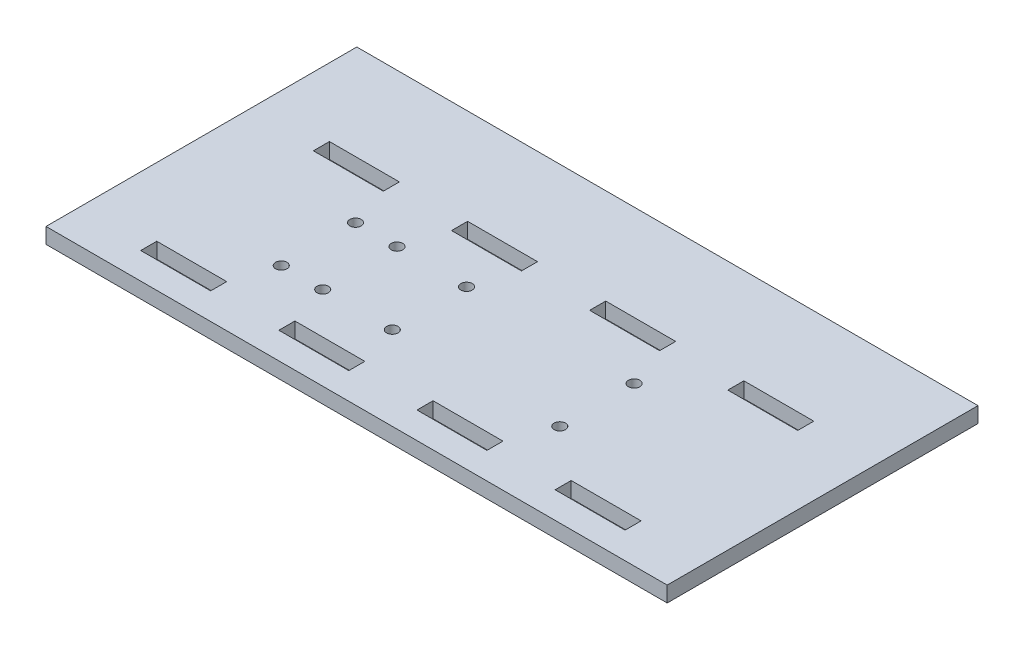
SolidWorks part; units mm, degrees
ref_plane "Front Plane" through (0, 0, 0) normal (0, 0, 1) x (1, 0, 0)
ref_plane "Top Plane" through (0, 0, 0) normal (0, 1, 0) x (1, 0, 0)
ref_plane "Right Plane" through (0, 0, 0) normal (1, 0, 0) x (0, 0, -1)
sketch "Sketch2" plane through (0, 0, 0) normal (0, 1, 0) x (1, 0, 0)
  line L3 (110, 45) -> (-110, 45)
  line L4 (110, 45) -> (110, -45)
  line L5 (110, -45) -> (-110, -45)
  line L6 (-110, 45) -> (-110, -45)
  line L7 (110, 45) -> (-110, -45) construction
  line L8 (110, -45) -> (-110, 45) construction
  point P0 (0, 0)
  dimension "D1" = 220
  dimension "D2" = 90
extrude "Boss-Extrude1" add sketch "Sketch2" along normal blind 4.5
sketch "Sketch3" plane through (0, 0, 0) normal (0, -1, 0) x (1, 0, 0)
  line L0 (0, 0) -> (0, -15) construction
  line L1 (50.125, -12.675) -> (50.125, -17.325)
  line L2 (10.125, -12.675) -> (-10.125, -12.675)
  line L3 (10.125, -12.675) -> (10.125, -17.325)
  line L4 (10.125, -17.325) -> (-10.125, -17.325)
  line L5 (-10.125, -12.675) -> (-10.125, -17.325)
  line L6 (10.125, -12.675) -> (-10.125, -17.325) construction
  line L7 (10.125, -17.325) -> (-10.125, -12.675) construction
  line L8 (50.125, -12.675) -> (29.875, -12.675)
  line L9 (29.875, -12.675) -> (29.875, -17.325)
  line L10 (50.125, -17.325) -> (29.875, -17.325)
  line L11 (90.125, -12.675) -> (90.125, -17.325)
  line L12 (90.125, -12.675) -> (69.875, -12.675)
  line L13 (69.875, -12.675) -> (69.875, -17.325)
  line L14 (90.125, -17.325) -> (69.875, -17.325)
  line L15 (10.125, -12.675) -> (50.125, -12.675) construction
  line L16 (-90.125, -17.325) -> (-69.875, -17.325)
  line L17 (-69.875, -12.675) -> (-69.875, -17.325)
  line L18 (-90.125, -12.675) -> (-69.875, -12.675)
  line L19 (-90.125, -12.675) -> (-90.125, -17.325)
  line L20 (-50.125, -17.325) -> (-29.875, -17.325)
  line L21 (-29.875, -12.675) -> (-29.875, -17.325)
  line L22 (-50.125, -12.675) -> (-29.875, -12.675)
  line L23 (-50.125, -12.675) -> (-50.125, -17.325)
  line L24 (0, 0) -> (0, 10) construction
  line L25 (0, 10) -> (-14.7938, 10) construction
  line L26 (10.125, 32.675) -> (50.125, 32.675) construction
  line L27 (10.125, 37.325) -> (-10.125, 32.675) construction
  line L28 (10.125, 32.675) -> (-10.125, 37.325) construction
  line L29 (-50.125, 32.675) -> (-50.125, 37.325)
  line L30 (-50.125, 32.675) -> (-29.875, 32.675)
  line L31 (-29.875, 32.675) -> (-29.875, 37.325)
  line L32 (-50.125, 37.325) -> (-29.875, 37.325)
  line L33 (-90.125, 32.675) -> (-90.125, 37.325)
  line L34 (-90.125, 32.675) -> (-69.875, 32.675)
  line L35 (-69.875, 32.675) -> (-69.875, 37.325)
  line L36 (-90.125, 37.325) -> (-69.875, 37.325)
  line L37 (90.125, 37.325) -> (69.875, 37.325)
  line L38 (69.875, 32.675) -> (69.875, 37.325)
  line L39 (90.125, 32.675) -> (69.875, 32.675)
  line L40 (90.125, 32.675) -> (90.125, 37.325)
  line L41 (50.125, 37.325) -> (29.875, 37.325)
  line L42 (29.875, 32.675) -> (29.875, 37.325)
  line L43 (50.125, 32.675) -> (29.875, 32.675)
  line L44 (-10.125, 32.675) -> (-10.125, 37.325)
  line L45 (10.125, 37.325) -> (-10.125, 37.325)
  line L46 (10.125, 32.675) -> (10.125, 37.325)
  line L47 (10.125, 32.675) -> (-10.125, 32.675)
  line L48 (50.125, 32.675) -> (50.125, 37.325)
  dimension "D1" = 15
  dimension "D2" = 20.25
  dimension "D3" = 4.65
  dimension "D5" = 40
  dimension "D6" = 10
  dimension "D4" = 3
extrude "Cut-Extrude1" cut sketch "Sketch3" against normal through all
sketch "Sketch4" plane through (0, 0, 0) normal (0, -1, 0) x (1, 0, 0)
  line L0 (0, 5) -> (40, 5) construction
  line L1 (0, 0) -> (0, 5) construction
  line L2 (60, 12.5) -> (20, 12.5)
  line L3 (60, 12.5) -> (60, -2.5)
  line L4 (60, -2.5) -> (20, -2.5)
  line L5 (20, 12.5) -> (20, -2.5)
  line L6 (60, 12.5) -> (20, -2.5) construction
  line L7 (60, -2.5) -> (20, 12.5) construction
  dimension "D1" = 40
  dimension "D2" = 15
  dimension "D3" = 5
  dimension "D4" = 40
extrude "Input link cut" [suppressed] cut sketch "Sketch4" against normal through all
sketch "Sketch5" plane through (0, 0, 0) normal (0, -1, 0) x (1, 0, 0)
  line L0 (54.65, 37.25) -> (54.65, -17.25) construction
  line L1 (56.9, 37.25) -> (52.4, 37.25) construction
  line L2 (52.4, -17.25) -> (56.9, -17.25) construction
  line L3 (6.15, 32.75) -> (6.15, -17.325) construction
  line L4 (3.9, 32.75) -> (8.4, 32.75) construction
  line L5 (-10.125, -17.325) -> (10.125, -17.325) construction
  line L6 (-26, -17.25) -> (-26, 37.25) construction
  line L7 (-27.75, -17.25) -> (-24.25, -17.25) construction
  line L8 (-24.25, 37.25) -> (-27.75, 37.25) construction
  line L9 (-14, -17.25) -> (-14, 37.25) construction
  line L10 (-15.75, -17.25) -> (-12.25, -17.25) construction
  line L11 (-12.25, 37.25) -> (-15.75, 37.25) construction
  line L12 (-26, 20.75) -> (58.5718, 20.75) construction
  line L13 (-10, 32.75) -> (-30, 32.75) construction
  line L14 (-26, 10) -> (-62.5697, 10) construction
  circle A0 centre (-26, 20.75) radius 1.65
  circle A1 centre (-14, 20.75) radius 1.65
  circle A2 centre (6.15, 20.75) radius 1.65
  circle A3 centre (54.65, 20.75) radius 1.65
  circle A4 centre (54.65, -0.75) radius 1.65
  circle A5 centre (6.15, -0.75) radius 1.65
  circle A6 centre (-14, -0.75) radius 1.65
  circle A7 centre (-26, -0.75) radius 1.65
  dimension "D2" = 3.3
  dimension "D1" = 12
extrude "Bracket holes" cut sketch "Sketch5" against normal through all
sketch "Sketch6" plane through (0, 0, 0) normal (0, -1, 0) x (1, 0, 0)
  line L0 (-69.875, -17.325) -> (-69.875, -12.675) construction
  line L1 (-129.3037, 54.0171) -> (-69.875, 54.0171)
  line L2 (-129.3037, 54.0171) -> (-129.3037, -58.1717)
  line L3 (-129.3037, -58.1717) -> (-69.875, -58.1717)
  line L4 (-69.875, 54.0171) -> (-69.875, -58.1717)
extrude "Trim cut" cut sketch "Sketch6" against normal through all
